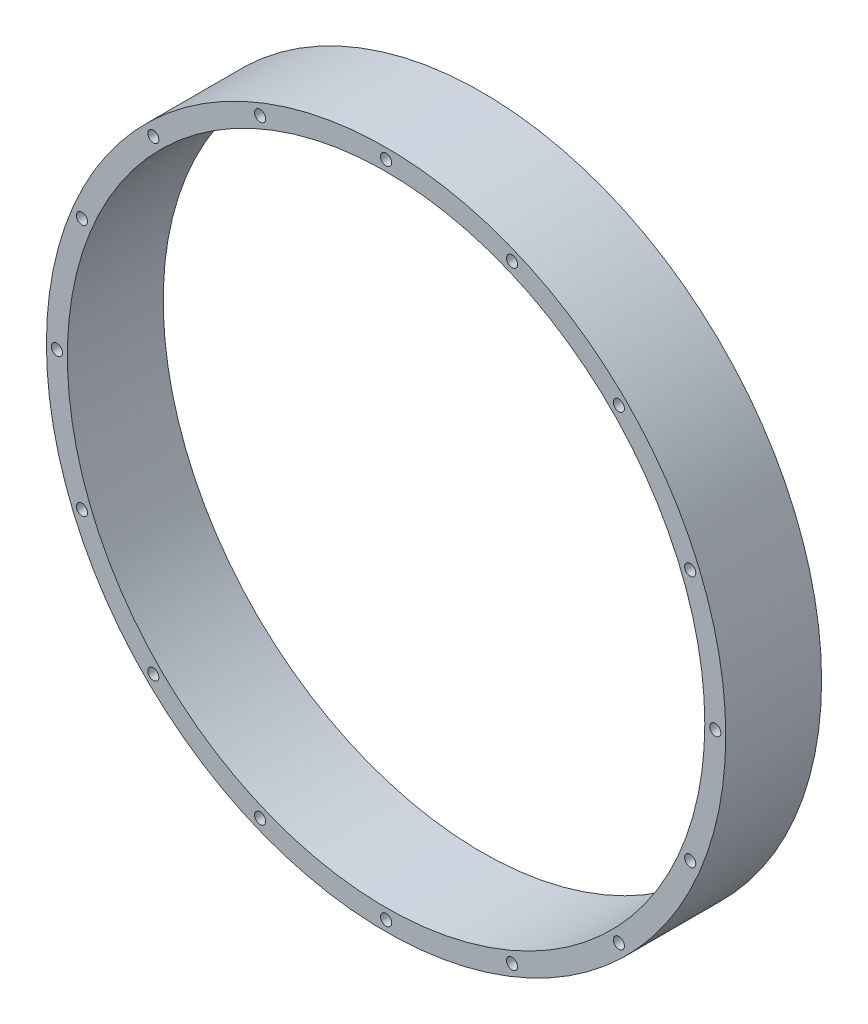
SolidWorks part; units mm, degrees
ref_plane "Front Plane" through (0, 0, 0) normal (1, 0, 0) x (0, 1, 0)
ref_plane "Top Plane" through (0, 0, 0) normal (0, 0, 1) x (0, 1, 0)
ref_plane "Right Plane" through (0, 0, 0) normal (0, 1, 0) x (-1, 0, 0)
sketch "Sketch1" plane through (0, 0, 0) normal (0, 0, 1) x (0, 1, 0)
  line L0 (0, 143) -> (0, 152.4) construction
  circle A0 centre (0, 0) radius 143
  circle A1 centre (0, 0) radius 152.4
  circle A2 centre (0, 147.7) radius 2.4892
  dimension "D1" = 304.8
  dimension "D2" = 286
  dimension "D3" = 4.9784
extrude "Boss-Extrude1" add sketch "Sketch1" against normal blind 43 contours A2 L0 | L0 A2 | A0 A2 A1 region at (-104.7151, 104.7151, 0) region at (-147.7, -1.0564, 0) region at (-147.7, 1.0564, 0)
extrude "Cut-Extrude1" cut sketch "Sketch1<3>" against normal through all contours A2 L0 | L0 A2 region at (-147.7, -1.0564, 0) region at (-147.7, 1.0564, 0)
sketch "Sketch1<3>" plane through (0, 0, 0) normal (0, 0, 1) x (0, 1, 0) same geometry as "Sketch1"
pattern_circular "CirPattern1" count 16 over 360 about axis through (0, 0, -43) along (0, 0, 1) of "Cut-Extrude1"
